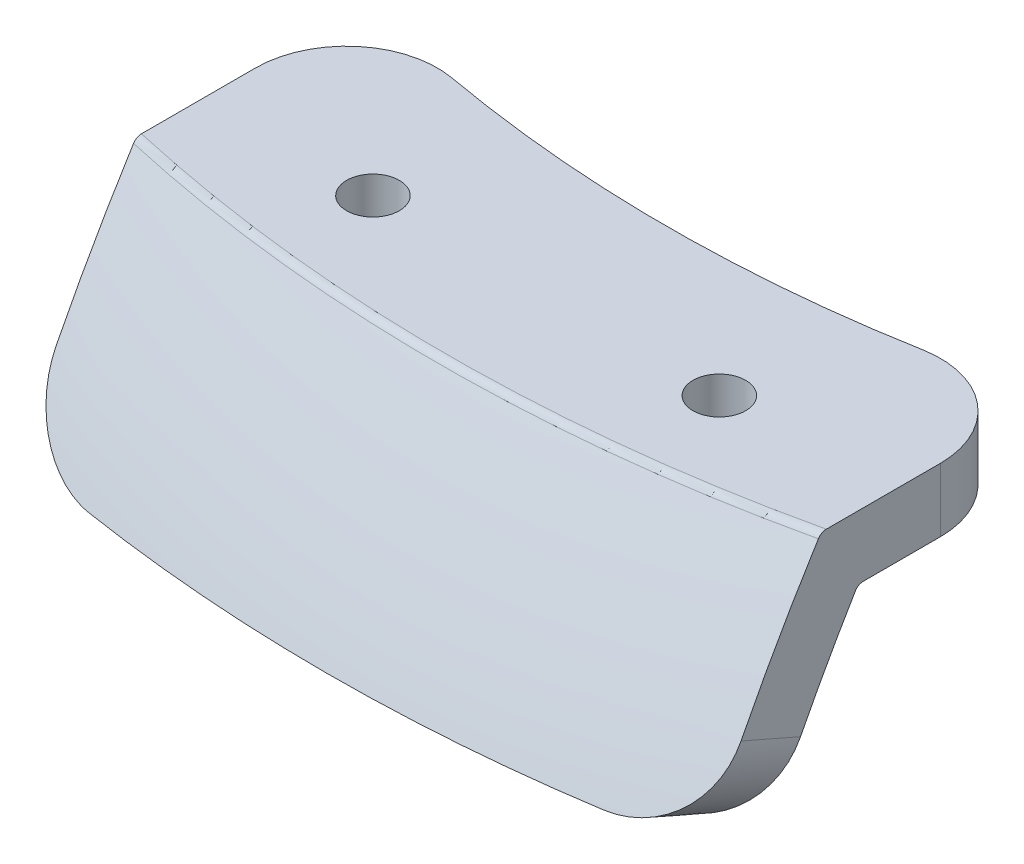
SolidWorks part; units mm, degrees
material "Polyether Polyol"
ref_plane "Front Plane" through (0, 0, 0) normal (0, 0, 1) x (1, 0, 0)
ref_plane "Top Plane" through (0, 0, 0) normal (0, 1, 0) x (1, 0, 0)
ref_plane "Right Plane" through (0, 0, 0) normal (1, 0, 0) x (0, 0, -1)
sketch "Sketch1" plane through (0, 0, 0) normal (1, 0, 0) x (0, 0, -1)
  line L0 (-182.9297, 170.7997) -> (-176.5279, 167.9681) construction
  line L1 (-170.3849, 194.6685) -> (-145.5262, 194.6685) construction
  line L9 (-145.5262, 194.6685) -> (-145.5262, 187.6685) construction
  line L10 (-145.5262, 187.6685) -> (-166.4259, 187.6685) construction
  line L11 (-182.9297, 170.7997) -> (-176.5279, 167.9681)
  line L12 (-170.3849, 194.6685) -> (-145.5262, 194.6685)
  line L13 (-145.5262, 194.6685) -> (-145.5262, 187.6685)
  line L14 (-145.5262, 187.6685) -> (-166.4259, 187.6685)
  line L15 (0, 0) -> (0, 89.8878) construction
  arc A5 (-166.4259, 187.6685) -> (-176.5279, 167.9681) centre (0, 89.8878) ccw construction
  arc A6 (-170.3849, 194.6685) -> (-182.9297, 170.7997) centre (0, 89.8878) ccw construction
  arc A7 (-166.4259, 187.6685) -> (-176.5279, 167.9681) centre (0, 89.8878) ccw
  arc A8 (-170.3849, 194.6685) -> (-182.9297, 170.7997) centre (0, 89.8878) ccw
revolve "Revolve1" add sketch "Sketch1" angle 30 mid plane about L15
sketch "Sketch2" plane through (0, 0, 0) normal (-1, 0, 0) x (0, 0, 1)
  line L0 (0, 89.8878) -> (171.9865, 177.5193) construction
  line L3 (0, -200000) -> (0, 218797.9879) construction
  arc A0 (176.5279, 167.9681) -> (166.4259, 187.6685) centre (0, 89.8878) ccw construction
  dimension "D1" = 63
ref_plane "Plane1" through (0, 71.3612, -36.3604) normal (0, -0.891, 0.454) x (0, 0.454, 0.891)
sketch "Sketch4" plane through (0, 71.3612, -36.3604) normal (0, -0.891, 0.454) x (0, 0.454, 0.891)
  line L0 (219.8801, 19.237) -> (239.1484, 20.9228) construction
  line L1 (219.7494, 20.7313) -> (239.0177, 22.4171)
  line L2 (219.7494, 20.7313) -> (219.8801, 19.237)
  line L3 (40.8082, 0) -> (233.8332, 0) construction
  line L4 (219.8801, 19.237) -> (239.1484, 20.9228)
  line L5 (239.0177, 22.4171) -> (239.1484, 20.9228)
  dimension "D1" = 3
  dimension "D2" = 5
revolve "Cut-Revolve1" cut sketch "Sketch4" angle 360 about L0
mirror "Mirror1" about plane through (0, 0, 0) normal (1, 0, 0) of "Cut-Revolve1"
sketch "Sketch5" plane through (0, 0, 0) normal (0, 1, 0) x (1, 0, 0)
  line L1 (37.665, -140.5675) -> (-37.665, -140.5675)
  line L2 (37.665, -140.5675) -> (37.665, -182.9297)
  line L3 (37.665, -182.9297) -> (-37.665, -182.9297)
  line L4 (-37.665, -140.5675) -> (-37.665, -182.9297)
  arc A0 (-47.3457, -176.6965) -> (47.3457, -176.6965) centre (0, 0) ccw construction
extrude "Cut-Extrude2" cut sketch "Sketch5" along normal through all flip side to cut
fillet "Fillet1" radius 10 4 edges at (-37.665, 191.1685, 140.5675) (37.665, 191.1685, 140.5675)
fillet "Fillet2" radius 1 2 edges at (0, 194.6685, 170.3849) (0, 187.6685, 166.4259)
sketch "Sketch6" plane through (0, 194.6685, 0) normal (0, 1, 0) x (1, 0, 0)
  circle A0 centre (19.05, -158.75) radius 2.9 construction
  circle A1 centre (-19.05, -158.75) radius 2.9 construction
  circle A2 centre (19.05, -158.75) radius 2.9
  circle A3 centre (-19.05, -158.75) radius 2.9
extrude "Cut-Extrude3" cut sketch "Sketch6" against normal through all
